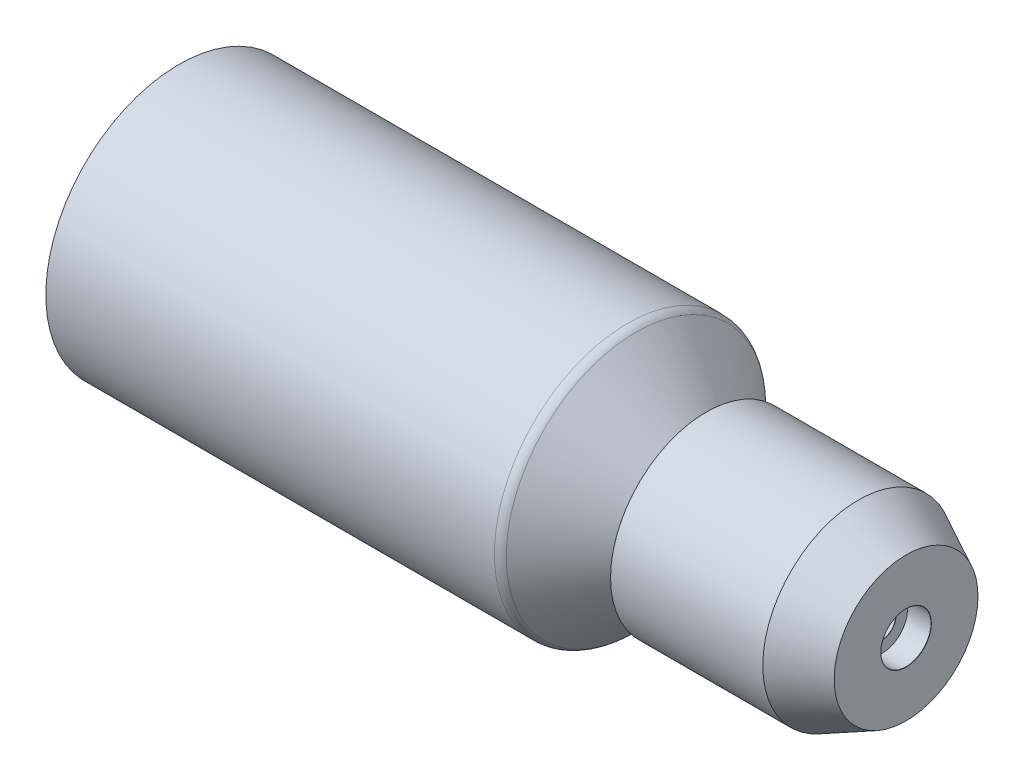
SolidWorks part; units mm, degrees
ref_plane "Front Plane" through (0, 0, 0) normal (0, 0, 1) x (1, 0, 0)
ref_plane "Top Plane" through (0, 0, 0) normal (0, 1, 0) x (1, 0, 0)
ref_plane "Right Plane" through (0, 0, 0) normal (1, 0, 0) x (0, 0, -1)
sketch "Sketch3" plane through (0, 0, 0) normal (0, 0, 1) x (1, 0, 0)
  line L0 (1.7986, 24.13) -> (-76.2, 24.13) construction
  line L1 (-76.2, 17.78) -> (-76.2, 11.43)
  line L2 (-76.2, 24.13) -> (-76.2, 17.78) construction
  line L3 (-76.2, 17.78) -> (-16.3214, 17.78)
  line L4 (-15.1989, 17.315) -> (-5.8214, 7.9375)
  line L5 (-5.8214, 7.9375) -> (-5.8214, -7.9375) construction
  line L6 (-5.8214, 12.7) -> (-5.8214, -12.7) construction
  line L7 (-5.8214, 7.9375) -> (-5.8214, 12.7762)
  line L8 (-5.8214, 12.7762) -> (1.7986, 12.7762)
  line L9 (1.7986, 24.1554) -> (1.7986, -24.1554) construction
  line L10 (1.7986, 12.7762) -> (1.7986, 24.13) construction
  line L11 (24.1721, 0) -> (-63.4646, 0) construction
  line L12 (-76.2, 11.43) -> (-15.6639, 11.43)
  line L13 (-15.6639, 11.43) -> (-15.6639, 0)
  line L14 (-15.6639, 0) -> (-5.8214, 0)
  line L15 (-5.8214, 0) -> (-5.8214, 7.9375) construction
  line L16 (-15.6639, 17.78) -> (-15.6639, 11.43) construction
  line L18 (1.7986, 0) -> (-5.8214, 0)
  line L19 (1.7986, 12.7762) -> (20.8486, 12.7762)
  line L20 (20.8486, 12.7762) -> (20.8486, 0)
  line L21 (20.8486, 0) -> (1.7986, 0)
  arc A0 (-16.3214, 17.78) -> (-15.1989, 17.315) centre (-16.3214, 16.1925) cw
  dimension "D7" = 1.5875
  dimension "D1" = 45
  dimension "D2" = 12.7762
  dimension "D3" = 6.35
  dimension "D4" = 24.13
  dimension "D5" = 15.875
  dimension "D6" = 76.2
  dimension "D8" = 6.35
  dimension "D9" = 19.05
revolve "Revolve1" add sketch "Sketch3" angle 360 about L11
hole_wizard "CBORE for M3 SBHCS1" positions "Sketch4" profile "Sketch6" counterbore size "M3" standard "ANSI Metric" end condition through all
sketch "Sketch4" plane through (-15.6639, 0, 0) normal (-1, 0, 0) x (0, 0, 1)
  point P0 (0, 0)
sketch "Sketch6" plane through (-15.6639, 0, 0) normal (0, 1, 0) x (0, 0, 1)
  line L0 (0, 0) -> (0, 36.5125)
  line L1 (0, 36.5125) -> (1.8, 36.5125)
  line L3 (1.8, 36.5125) -> (1.8, 1.65)
  line L4 (3.35, 1.65) -> (1.8, 1.65)
  line L5 (3.35, 1.65) -> (3.35, 0.025)
  line L6 (3.35, 0.025) -> (3.375, 0)
  line L7 (3.375, 0) -> (0, 0)
  line L8 (-3.35, 0.025) -> (-3.375, 0) construction
  line L11 (0, -6.35) -> (0, 107.95) construction
  dimension "Thru Hole Dia." = 3.6
  dimension "Thru Hole Depth" = 36.5125
  dimension "C'Bore Dia." = 6.7
  dimension "C'Bore Depth" = 1.65
  dimension "Near C'Sink Dia." = 6.75
  dimension "Near C'Sink Angle" = 90
ref_plane "split-plane" through (-5.8214, 0, 0) normal (-1, 0, 0) x (0, 0, 1)
sketch "Sketch10" plane through (0, 0, 0) normal (1, 0, 0) x (0, 0, -1)
  circle A3 centre (0, 0) radius 12.7762
  point P0 (0, 0)
  dimension "D2" = 25.5524
extrude "Boss-Extrude1" add sketch "Sketch10" along normal blind 19.05
chamfer "Chamfer1" distance 6.35 distance2 3.175 1 edges at (20.8486, 0, -12.7762) first distance on face at (20.8486, 0, -12.7762)
hole_wizard "CBORE for M3 SBHCS3" positions "Sketch11" profile "Sketch12" counterbore size "M3" standard "ANSI Metric" end condition through all
sketch "Sketch11" plane through (20.8486, 0, 0) normal (1, 0, 0) x (0, 0, -1)
  point P0 (0, 0)
sketch "Sketch12" plane through (20.8486, 0, 0) normal (0, 1, 0) x (0, 0, -1)
  line L0 (0, 0) -> (0, 97.0486)
  line L1 (0, 97.0486) -> (1.8, 97.0486)
  line L3 (1.8, 3.2) -> (1.825, 3.175)
  line L4 (1.825, 3.175) -> (3.35, 3.175)
  line L5 (3.35, 3.175) -> (3.35, 0.025)
  line L6 (3.35, 0.025) -> (3.375, 0)
  line L7 (3.375, 0) -> (0, 0)
  line L8 (-3.35, 0.025) -> (-3.375, 0) construction
  line L9 (-1.8, 3.2) -> (-1.825, 3.175) construction
  line L10 (1.8, 97.0486) -> (1.8, 3.2)
  line L11 (0, -6.35) -> (0, 107.95) construction
  dimension "Thru Hole Dia." = 3.6
  dimension "Thru Hole Depth" = 97.0486
  dimension "C'Bore Dia." = 6.7
  dimension "C'Bore Depth" = 3.175
  dimension "Near C'Sink Dia." = 6.75
  dimension "Near C'Sink Angle" = 90
  dimension "Mid C'Sink Dia." = 3.65
  dimension "Mid C'Sink Angle" = 90
split "split" trim tools "split-plane" bodies to split 107 resulting bodies 104 105
